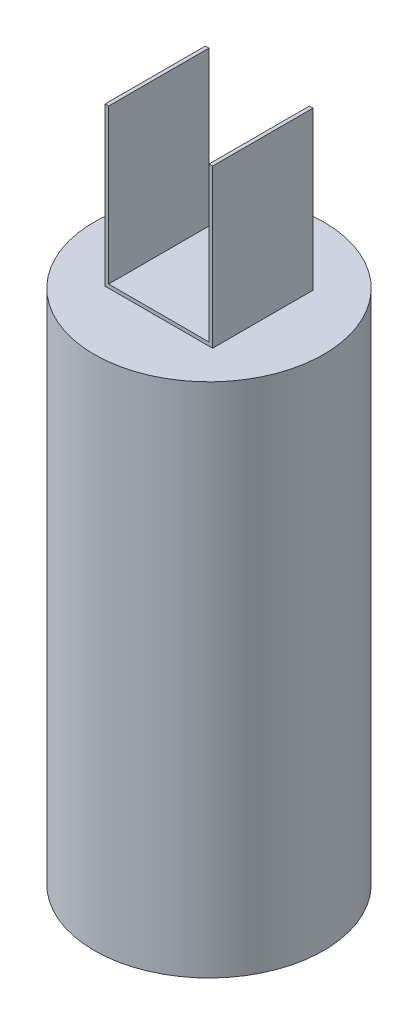
SolidWorks part; units mm, degrees
ref_plane "Front Plane" through (0, 0, 0) normal (0, 0, 1) x (1, 0, 0)
ref_plane "Top Plane" through (0, 0, 0) normal (0, 1, 0) x (1, 0, 0)
ref_plane "Right Plane" through (0, 0, 0) normal (1, 0, 0) x (0, 0, -1)
sketch "Sketch1" plane through (0, 0, 0) normal (0, 1, 0) x (1, 0, 0)
  circle A0 centre (0, 0) radius 101.6
  dimension "D1" = 203.2
extrude "Boss-Extrude1" add sketch "Sketch1" along normal blind 457.2
sketch "Sketch2" plane through (0, 457.2, 0) normal (0, 1, 0) x (1, 0, 0)
  line L1 (-47.625, 44.45) -> (47.625, 44.45)
  line L2 (-47.625, 44.45) -> (-47.625, -44.45)
  line L3 (-47.625, -44.45) -> (47.625, -44.45)
  line L4 (47.625, 44.45) -> (47.625, -44.45)
  line L5 (-47.625, 44.45) -> (47.625, -44.45) construction
  line L6 (-47.625, -44.45) -> (47.625, 44.45) construction
  line L7 (-44.45, -44.45) -> (44.45, -44.45)
  line L8 (-44.45, -44.45) -> (-44.45, 44.45)
  line L9 (-44.45, 44.45) -> (44.45, 44.45)
  line L10 (44.45, -44.45) -> (44.45, 44.45)
  line L11 (-44.45, -44.45) -> (44.45, 44.45) construction
  line L12 (-44.45, 44.45) -> (44.45, -44.45) construction
  point P0 (0, 0)
  point P6 (0, 0)
  dimension "D1" = 95.25
  dimension "D2" = 88.9
  dimension "D3" = 88.9
extrude "Boss-Extrude3" add sketch "Sketch2" along normal blind 139.7 contours L10 L3 L4 L1 | L3 L8 L1 L2 region at (-46.0375, 457.2, 0) region at (46.0375, 457.2, 0)
extrude "Boss-Extrude4" add sketch "Sketch2<3>" along normal blind 3.175 contours L3 L10 L1 L8 region at (0, 457.2, 0)
sketch "Sketch2<3>" plane through (0, 457.2, 0) normal (0, 1, 0) x (1, 0, 0) same geometry as "Sketch2"
